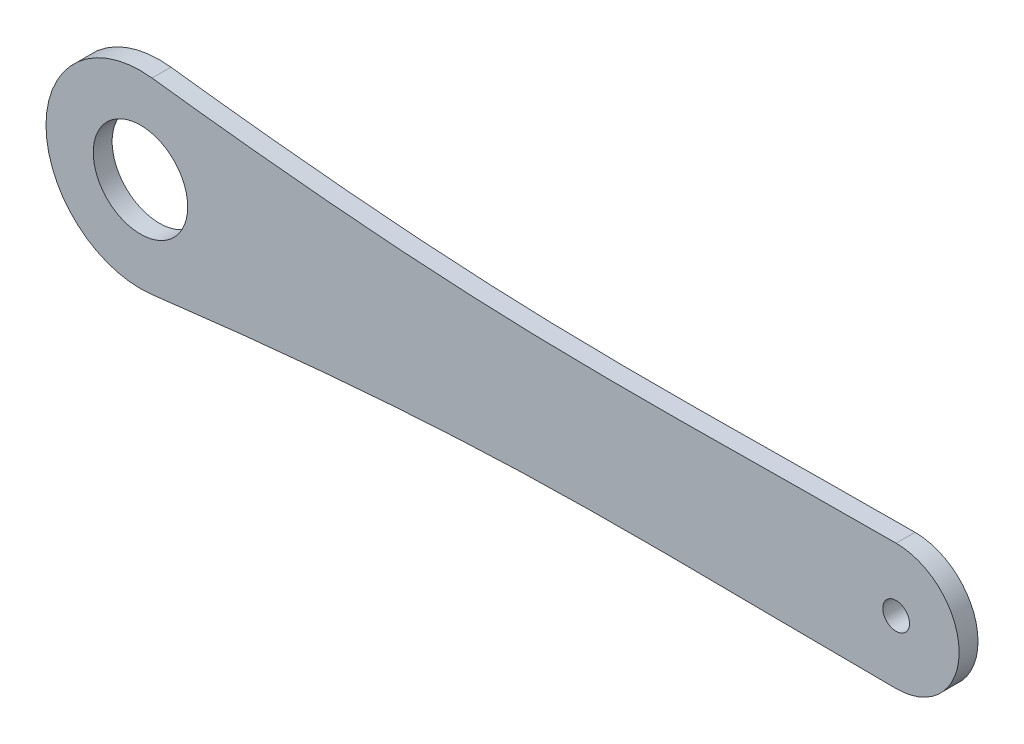
SolidWorks part; units mm, degrees
ref_plane "Front Plane" through (0, 0, 0) normal (0, 0, 1) x (1, 0, 0)
ref_plane "Top Plane" through (0, 0, 0) normal (0, 1, 0) x (1, 0, 0)
ref_plane "Right Plane" through (0, 0, 0) normal (1, 0, 0) x (0, 0, -1)
sketch "Sketch1" plane through (0, 0, 0) normal (0, 0, 1) x (1, 0, 0)
  line L0 (-103.1351, 0) -> (103.1351, 0) construction
  line L3 (0, 10) -> (0, -10) construction
  circle A2 centre (-60, 0) radius 7.5
  circle A3 centre (60, 0) radius 2.125
  arc A4 (-58.1622, 14.887) -> (-58.1622, -14.887) centre (-60, 0) ccw
  arc A5 (60, -10) -> (60, 10) centre (60, 0) ccw
  spline S0 degree 3 poles (60, 10) (39.9389, 10) (0.5184, 8.7165) (-38.8032, 12.4971) (-58.1622, 14.887) knots 0 0 0 0 0.506898 1 1 1 1
  spline S1 degree 3 poles (60, -10) (39.9389, -10) (0.5184, -8.7165) (-38.8032, -12.4971) (-58.1622, -14.887) knots 0 0 0 0 0.506898 1 1 1 1
  point P7 (0, 0)
  dimension "D3" = 15
  dimension "D1" = 4.25
  dimension "D2" = 30
  dimension "D4" = 20
  dimension "D5" = 120
  dimension "D6" = 20
  dimension "D7" = 60
extrude "Boss-Extrude1" add sketch "Sketch1" along normal blind 3
equation "\"L1\"= 120mm'Upper arm"
equation "\"L3\"= 75mm'Wrist→TCP"
equation "\"h0\"= 75mm'Shoulder height"
equation "\"t_link\"= 3mm'Link plate thickness"
equation "\"t_bracket\"= 4mm'Bracket thickness"
equation "\"d_pin\"= 4mm'Pin diameter (M4)"
equation "\"c_fit\"= 0.2mm'Nominal clearance - measured PLA 2026-10-01"
equation "\"L2\"= 120mm'Forearm"
equation "\"c_fit_pivot\"= \"c_fit\" + 0.05mm'Gripper pivot clearance - chosen 0.25 mm 2026-10-01"
equation "\"d_pin_gripper\"= 3mm'Gripper pivot diameter"
equation "\"w_link\"= 20mm'Link plate depth (bending direction)"
equation "\"w_gap\"= 20mm'Twin-plate gap - provisional, set by elbow servo mount"
equation "\"D1@Boss-Extrude1\"=\"t_link\""
equation "\"d_boss\"= 13mm'MG996R output boss dia - from downloaded model, verify with calipers"
equation "\"c_boss\"= 1mm'Radial clearance around servo boss"
equation "\"d_servo_hole\"= \"d_boss\" + 2 * \"c_boss\"'Plate clearance hole for servo boss (15 mm)"
equation "\"t_rim\"= 7.5mm'Min material around servo hole (M3 bolt ring + edge)"
equation "\"w_link_end\"= \"d_servo_hole\" + 2 * \"t_rim\"'Link plate end width at servo end (30 mm)"
equation "\"d_hole_m3\"= \"d_pin_gripper\" + \"c_fit\"'M3 bolt clearance hole (spacer and adapter bolts)"
equation "\"d_hole_pivot\"= \"d_pin\" + \"c_fit_pivot\"'M4 pivot hole where the pin rotates (4.25 mm)"
equation "\"D3@Sketch1\"=\"d_servo_hole\""
equation "\"D1@Sketch1\"=\"d_pin\"+\"c_fit_pivot\""
equation "\"D2@Sketch1\"=\"w_link_end\""
equation "\"D4@Sketch1\"=\"w_link\""
equation "\"D5@Sketch1\"=\"L1\""
equation "\"D6@Sketch1\"=\"w_link\""
